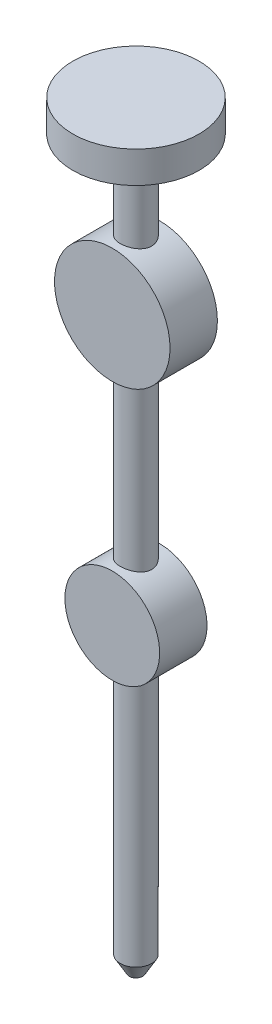
SolidWorks part; units mm, degrees
ref_plane "前视基准面" through (0, 0, 0) normal (0, 0, 1) x (1, 0, 0)
ref_plane "上视基准面" through (0, 0, 0) normal (0, 1, 0) x (1, 0, 0)
ref_plane "右视基准面" through (0, 0, 0) normal (1, 0, 0) x (0, 0, -1)
sketch "草图1" plane through (0, 0, 0) normal (0, 1, 0) x (1, 0, 0)
  circle A0 centre (0, 0) radius 40
extrude "凸台-拉伸1" add sketch "草图1" along normal blind 20 contours A0
sketch "草图2" plane through (0, 0, 0) normal (0, -1, 0) x (-1, 0, 0)
  circle A0 centre (0, 0) radius 10
  point P3 (0, 0)
extrude "凸台-拉伸2" add sketch "草图2" along normal blind 60
sketch "草图3" plane through (0, 0, 0) normal (0, 0, 1) x (1, 0, 0)
  circle A0 centre (0, -91.6768) radius 36.5903
extrude "凸台-拉伸3" add sketch "草图3" along normal blind 15 and the other way blind 15
sketch "草图5" plane through (0, 0, 0) normal (0, -1, 0) x (-1, 0, 0)
  circle A0 centre (0, 0) radius 10
split line "分割线2"
extrude "凸台-拉伸4" add sketch "草图2<2>" along normal blind 450
sketch "草图2<2>" plane through (0, 0, 0) normal (0, -1, 0) x (-1, 0, 0) same geometry as "草图2"
sketch "草图7" plane through (0, 0, -15) normal (0, 0, -1) x (-1, 0, 0)
  circle A0 centre (0, -262.1924) radius 30
extrude "凸台-拉伸5" add sketch "草图7" along normal blind 0.0001 and the other way blind 30
sketch "草图8" plane through (0, -450, 0) normal (0, -1, 0) x (1, 0, 0)
  circle A0 centre (0, 0) radius 10
  point P3 (0, 0)
extrude "凸台-拉伸6" add sketch "草图8" along normal blind 10 draft 30 and the other way blind 0.0001
